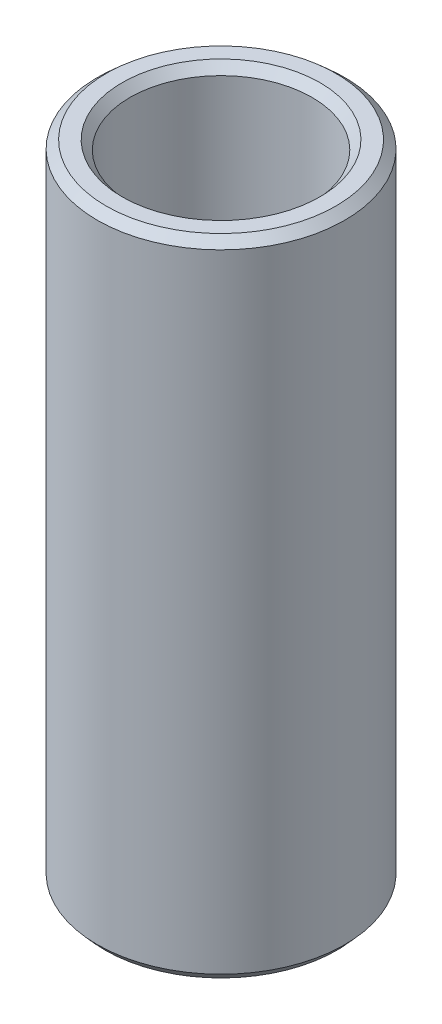
SolidWorks part; units mm, degrees
ref_plane "Front Plane" through (0, 0, 0) normal (0, 0, 1) x (1, 0, 0)
ref_plane "Top Plane" through (0, 0, 0) normal (0, 1, 0) x (1, 0, 0)
ref_plane "Right Plane" through (0, 0, 0) normal (1, 0, 0) x (0, 0, -1)
sketch "Sketch1" plane through (0, 0, 0) normal (0, 1, 0) x (1, 0, 0)
  circle A0 centre (0, 0) radius 55
  dimension "SLEEVE_OD" = 110
extrude "Boss-Extrude1" add sketch "Sketch1" along normal blind 286.3134
sketch "Sketch2" plane through (0, 0, 0) normal (0, 1, 0) x (1, 0, 0)
  circle A0 centre (0, 0) radius 40.4779
  dimension "BORE_D" = 80.9558
extrude "Cut-Extrude1" cut sketch "Sketch2" along normal through all
chamfer "Chamfer1" distance 3.5087 angle 48.201 4 edges at (0, 286.3134, 40.4779) (0, 0, 40.4779) (0, 0, 55) (0, 286.3134, 55) first distance on face at (0, 286.3134, 40.4779) first distance on face at (0, 0, 40.4779) first distance on face at (0, 286.3134, 55)
